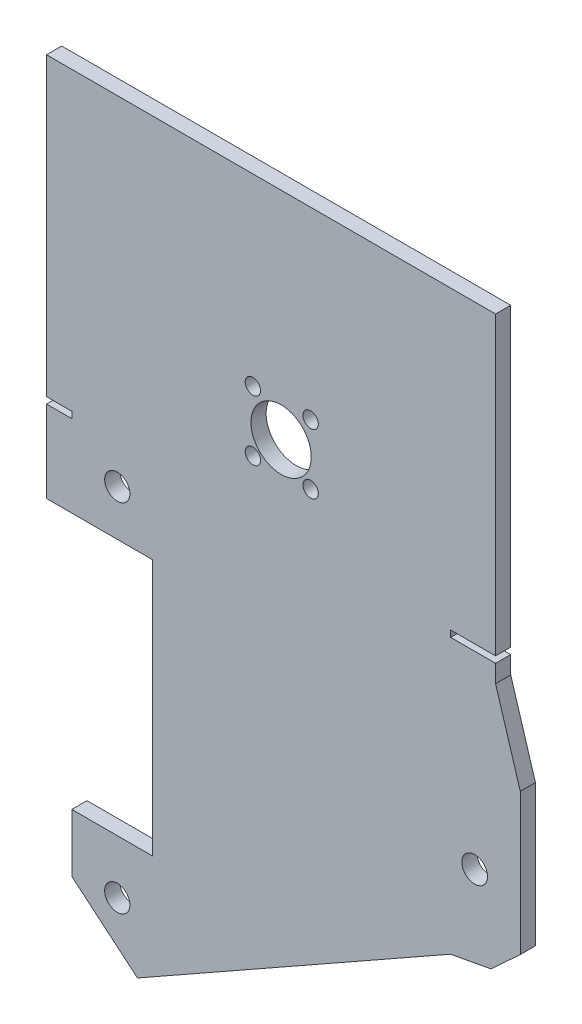
SolidWorks part; units mm, degrees
ref_plane "Front Plane" through (0, 0, 0) normal (0, 0, 1) x (1, 0, 0)
ref_plane "Top Plane" through (0, 0, 0) normal (0, 1, 0) x (1, 0, 0)
ref_plane "Right Plane" through (0, 0, 0) normal (1, 0, 0) x (0, 0, -1)
sketch "Sketch1" plane through (0, 0, 0) normal (0, 0, 1) x (1, 0, 0)
  line L0 (0, 0) -> (88.9, 0)
  line L1 (88.9, 0) -> (88.9, -3.5)
  line L2 (88.9, -3.5) -> (93.7917, -19.5)
  line L3 (93.7917, -19.5) -> (93.7917, -47.5)
  line L4 (0, 0) -> (0, -16.2)
  line L5 (0, -16.2) -> (21, -16.2)
  line L6 (21, -16.2) -> (21, -67)
  line L7 (21, -67) -> (5, -67)
  line L8 (5, -67) -> (5, -78.5)
  line L9 (5, -78.5) -> (18, -89.4083)
  line L10 (18, -89.4083) -> (80, -54.3304)
  line L11 (80, -54.3304) -> (88, -52.8477)
  line L12 (88, -52.8477) -> (93.7917, -47.5)
  dimension "D1" = 88.9
  dimension "D2" = 3.5
  dimension "D3" = 163
  dimension "D4" = 16
  dimension "D5" = 28
  dimension "D6" = 89.4083
  dimension "D7" = 21
  dimension "D8" = 50.8
  dimension "D9" = 16
  dimension "D10" = 11.5
  dimension "D11" = 130
  dimension "D12" = 13
  dimension "D13" = 110.5
  dimension "D14" = 62
  dimension "D15" = 8
  dimension "D16" = 161
extrude "Boss-Extrude1" add sketch "Sketch1" along normal blind 3
sketch "Sketch2" plane through (0, 0, 0) normal (0, 1, 0) x (1, 0, 0)
  line L0 (45.8978, 14) -> (40.3978, 14) construction
  line L1 (0, -3) -> (88.9, -3)
  line L2 (0, -3) -> (0, 54)
  line L3 (0, 54) -> (88.9, 54)
  line L4 (88.9, -3) -> (88.9, 54)
  circle A0 centre (40.3978, 8.5) radius 1.5
  circle A1 centre (40.3978, 20) radius 1.5
  circle A2 centre (51.8978, 8.5) radius 1.5
  circle A3 centre (51.8978, 20) radius 1.5
  ellipse E0 centre (45.8978, 14) end of major axis (45.8978, 8) minor radius 5.5
  dimension "D9" = 3
  dimension "D10" = 3
  dimension "D11" = 3
  dimension "D12" = 3
  dimension "D1" = 88.9
  dimension "D2" = 57
  dimension "D3" = 45.8978
  dimension "D4" = 5.5
  dimension "D5" = 11.5
  dimension "D6" = 23
  dimension "D7" = 11.5
  dimension "D8" = 17
  dimension "D13" = 12
  dimension "D14" = 11
extrude "Boss-Extrude2" add sketch "Sketch2" along normal blind 3
ref_plane "Plane1" through (85.9, 0, 0) normal (1, 0, 0) x (0, 0, -1)
sketch "Sketch3" plane through (85.9, 0, 0) normal (1, 0, 0) x (0, 0, -1)
  line L0 (11.5, 0) -> (0, 0)
  line L1 (0, 0) -> (54, 0) construction
  line L2 (0, 0) -> (0, -11.5)
  line L3 (0, -19.5) -> (0, -3.5) construction
  line L4 (0, -11.5) -> (11.5, 0)
  dimension "D1" = 11.5
  dimension "D2" = 11.5
extrude "Boss-Extrude3" add sketch "Sketch3" against normal blind 84.5
sketch "Sketch4" plane through (0, 0, 0) normal (0, 0, -1) x (-1, 0, 0)
  line L0 (-1.4, -11.5) -> (-85.9, -11.5) construction
  line L1 (-81.4, -11.5) -> (-6.4, -11.5)
  line L2 (-81.4, -11.5) -> (-81.4, 0)
  line L3 (-81.4, 0) -> (-6.4, 0)
  line L4 (-6.4, -11.5) -> (-6.4, 0)
  line L5 (-50.8976, 0) -> (-85.9, 0) construction
  line L6 (-85.9, 13.7659) -> (-85.9, -13.7659) construction
  dimension "D1" = 75
  dimension "D2" = 4.5
extrude "Cut-Extrude2" cut sketch "Sketch4" along normal blind 84.5
sketch "Sketch6" plane through (0, 0, 3) normal (0, 0, 1) x (1, 0, 0)
  line L0 (0, 3) -> (0, -16.2) construction
  line L1 (0, 3) -> (88.9, 3) construction
  circle A0 centre (14, -77.66) radius 2.5
  circle A1 centre (84.763, -37.386) radius 2.54
  circle A2 centre (14, -7.16) radius 2.5
  dimension "D1" = 5
  dimension "D2" = 5
  dimension "D3" = 5.08
  dimension "D4" = 14
  dimension "D5" = 10.16
  dimension "D6" = 70.5
  dimension "D7" = 14
  dimension "D8" = 40.386
  dimension "D9" = 70.763
extrude "Cut-Extrude3" cut sketch "Sketch6" against normal blind 84.5
sketch "Sketch7" plane through (0, 0, 0) normal (0, -1, 0) x (1, 0, 0)
  line L1 (88.9, -54) -> (0, -54)
  line L2 (88.9, -54) -> (88.9, 0)
  line L3 (88.9, 0) -> (0, 0)
  line L4 (0, -54) -> (0, 0)
extrude "Cut-Extrude4" cut sketch "Sketch7" against normal through all both and the other way through all
sketch "Sketch8" plane through (0, 0, 0) normal (0, 0, -1) x (-1, 0, 0)
  line L0 (-88.9, 3) -> (0, 3) construction
  line L1 (-88.9, 3) -> (0, 3)
  line L2 (-88.9, 3) -> (-88.9, 59.896)
  line L3 (-88.9, 59.896) -> (0, 59.896)
  line L4 (0, 3) -> (0, 59.896)
  line L5 (-46.4351, 17.1224) -> (-40.4661, 17.1224) construction
  line L6 (-14, -77.66) -> (-84.763, -77.66) construction
  line L7 (-84.763, -77.66) -> (-84.763, -37.386) construction
  line L8 (-49.3815, -77.66) -> (-49.3815, 51.3441) construction
  line L9 (-58.3815, 3) -> (-58.3815, 17.1224) construction
  line L10 (-58.3815, 17.1224) -> (-46.4351, 17.1224) construction
  circle A0 centre (-46.4351, 17.1224) radius 5.969
  circle A1 centre (-40.8471, 23.4724) radius 1.524
  circle A2 centre (-40.8471, 11.5344) radius 1.524
  circle A3 centre (-52.2771, 23.4724) radius 1.524
  circle A4 centre (-52.2771, 11.5344) radius 1.524
  point P27 (-42.3019, 17.1224)
  dimension "D8" = 11.938
  dimension "D9" = 3.048
  dimension "D10" = 3.048
  dimension "D11" = 3.048
  dimension "D12" = 3.048
  dimension "D1" = 56.896
  dimension "D2" = 88.9
  dimension "D3" = 14.1224
  dimension "D4" = 5.588
  dimension "D5" = 2.9464
  dimension "D6" = 11.938
  dimension "D7" = 5.588
  dimension "D14" = 11.43
extrude "Boss-Extrude4" add sketch "Sketch8" against normal up to surface (3 mm away) up to face at (16.5, -77.66, 3)
sketch "Sketch10" plane through (0, 0, 0) normal (0, 0, -1) x (-1, 0, 0)
  line L0 (-88.9, -3.5) -> (-88.9, 59.896) construction
  line L1 (0, 0) -> (-5.08, 0)
  line L2 (0, 0) -> (0, 1.27)
  line L3 (0, 1.27) -> (-5.08, 1.27)
  line L4 (-5.08, 0) -> (-5.08, 1.27)
  line L5 (-80.01, 0) -> (-88.9, 0)
  line L6 (-80.01, 0) -> (-80.01, 1.27)
  line L7 (-80.01, 1.27) -> (-88.9, 1.27)
  line L8 (-88.9, 0) -> (-88.9, 1.27)
  dimension "D1" = 5.08
  dimension "D2" = 1.27
  dimension "D3" = 8.89
  dimension "D4" = 1.27
extrude "Cut-Extrude5" cut sketch "Sketch10" against normal blind 10
